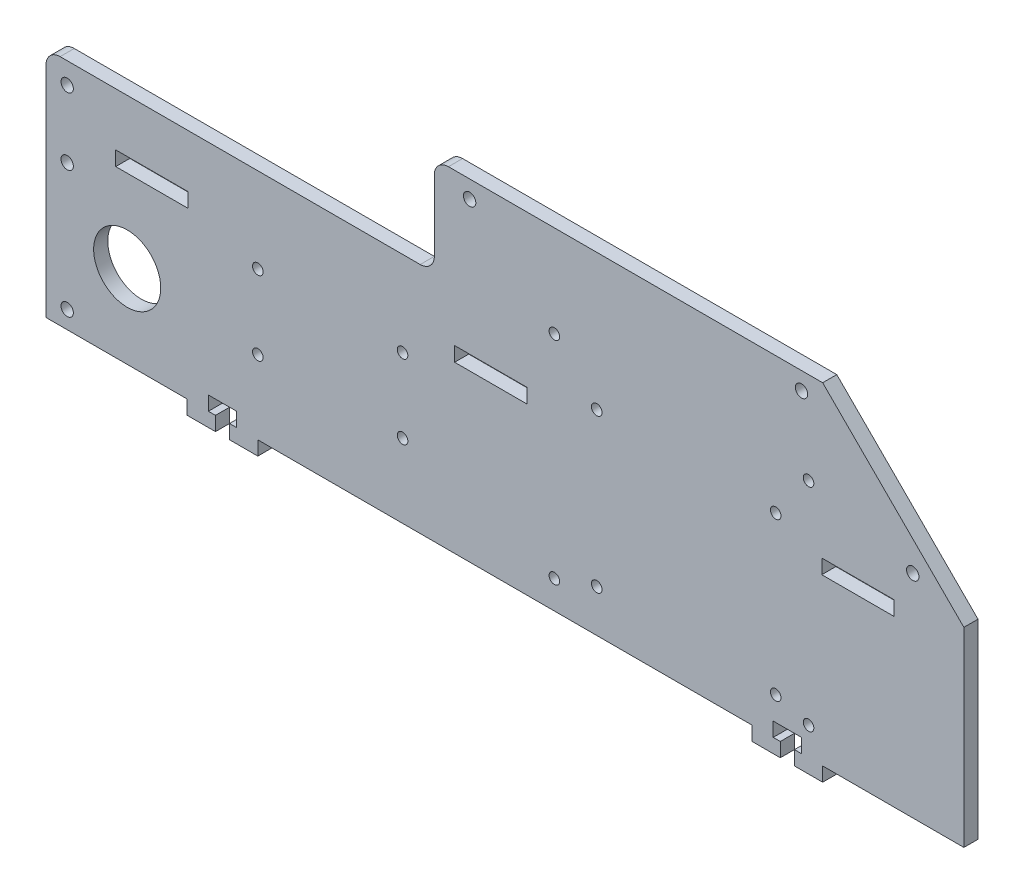
SolidWorks part; units mm, degrees
material "Ст 3 ГОСТ 380-88"
ref_plane "Спереди" through (0, 0, 0) normal (0, 0, 1) x (1, 0, 0)
ref_plane "Сверху" through (0, 0, 0) normal (0, 1, 0) x (1, 0, 0)
ref_plane "Справа" through (0, 0, 0) normal (1, 0, 0) x (0, 0, -1)
other "Configuration Table"
sketch "Эскиз1" plane through (0, 0, 0) normal (0, 0, 1) x (1, 0, 0)
  line L0 (52, -59) -> (60, -59)
  line L2 (0, 0) -> (0, -55)
  line L3 (0, -55) -> (40, -55)
  line L4 (260, -1) -> (260, -55)
  line L6 (40, -55) -> (40, -59)
  line L7 (40, -59) -> (48, -59)
  line L8 (60, -55) -> (60, -59)
  line L10 (200, -55) -> (200, -59)
  line L11 (200, -59) -> (208, -59)
  line L12 (220, -55) -> (220, -59)
  line L14 (48, -59) -> (48, -55)
  line L16 (52, -59) -> (52, -55)
  line L18 (46, -55) -> (46, -51)
  line L19 (46, -51) -> (54, -51)
  line L20 (54, -55) -> (54, -51)
  line L21 (46, -55) -> (48, -55)
  line L23 (52, -55) -> (54, -55)
  line L24 (60, -55) -> (200, -55)
  line L25 (206, -55) -> (208, -55)
  line L26 (212, -55) -> (214, -55)
  line L28 (208, -55) -> (208, -59)
  line L30 (212, -55) -> (212, -59)
  line L32 (206, -55) -> (206, -51)
  line L33 (206, -51) -> (214, -51)
  line L34 (214, -55) -> (214, -51)
  line L35 (220, -55) -> (260, -55)
  line L36 (120, 39) -> (220, 39)
  line L37 (19.75, -4) -> (40.25, -4)
  line L38 (19.75, -4) -> (19.75, -8.1)
  line L39 (212, -59) -> (220, -59)
  line L40 (19.75, -8.1) -> (40.25, -8.1)
  line L41 (40.25, -4) -> (40.25, -8.1)
  line L42 (219.75, -4.119) -> (240.25, -4.119)
  line L43 (219.75, -4.119) -> (219.75, -8.219)
  line L44 (219.75, -8.219) -> (240.25, -8.219)
  line L45 (240.25, -4.119) -> (240.25, -8.219)
  line L46 (115.75, -4) -> (136.25, -4)
  line L47 (115.75, -4) -> (115.75, -8.1)
  line L48 (115.75, -8.1) -> (136.25, -8.1)
  line L49 (136.25, -4) -> (136.25, -8.1)
  line L51 (0, 0) -> (0, 7)
  line L52 (4, 11) -> (106, 11)
  line L54 (114, 39) -> (120, 39)
  line L63 (110, 15) -> (110, 35)
  line L64 (260, -1) -> (220, 39)
  circle A0 centre (23, -31.5) radius 9.5
  arc A2 (106, 11) -> (110, 15) centre (106, 15) ccw
  arc A3 (110, 35) -> (114, 39) centre (114, 35) cw
  arc A4 (0, 7) -> (4, 11) centre (4, 7) cw
  circle A5 centre (23, -31.5) radius 17.5 construction
  circle A6 centre (156, -43) radius 1.5
  circle A8 centre (206.7, 0.4) radius 1.5
  circle A9 centre (156, 0.4) radius 1.5
  circle A12 centre (206.7, -43) radius 1.5
  circle A13 centre (206.7, -44.2) radius 1.5
  circle A14 centre (144, -47) radius 1.5
  circle A18 centre (216, -47) radius 1.5
  circle A19 centre (216, 13) radius 1.5
  circle A20 centre (144, 13) radius 1.5
  point P55 (0, 11)
  point P58 (0, -27.5)
  dimension "D28" = 19
  dimension "D38" = 54
  dimension "D39" = 4
  dimension "D42" = 35
  dimension "D43" = 3
  dimension "D49" = 44.6
  dimension "D51" = 3
  dimension "D53" = 3
  dimension "D2" = 55
  dimension "D3" = 4
  dimension "D4" = 20
  dimension "D5" = 40
  dimension "D6" = 4
  dimension "D7" = 20
  dimension "D8" = 40
  dimension "D9" = 4
  dimension "D10" = 2
  dimension "D11" = 2
  dimension "D12" = 4
  dimension "D13" = 8
  dimension "D14" = 4
  dimension "D15" = 8
  dimension "D16" = 4
  dimension "D17" = 2
  dimension "D18" = 2
  dimension "D19" = 4.1
  dimension "D20" = 28
  dimension "D21" = 19.75
  dimension "D22" = 20.5
  dimension "D23" = 4.1
  dimension "D24" = 20.5
  dimension "D25" = 115.75
  dimension "D26" = 19.75
  dimension "D27" = 20.5
  dimension "D29" = 23.5
  dimension "D30" = 23
  dimension "D31" = 4
  dimension "D32" = 110
  dimension "D33" = 66
  dimension "D34" = 94
  dimension "D35" = 40
  dimension "D36" = 260
  dimension "D37" = 56.5685
  dimension "D40" = 40
  dimension "D41" = 220
  dimension "D44" = 12
  dimension "D47" = 156
  dimension "D48" = 43.4
  dimension "D50" = 50.7
  dimension "D52" = 8
  dimension "D55" = 12
  dimension "D45" = 2
  dimension "D46" = 2
  dimension "D56" = 2
base flange "Базовая кромка1" sketch "Эскиз1" thickness 4 reverse thickness direction no parameters "D1"=0.7366
sketch "Эскиз6" plane through (0, 0, 0) normal (0, 0, 1) x (1, 0, 0)
  line L1 (0, 7) -> (0, -55) construction
  line L2 (0, 7) -> (0, -55) construction
  line L3 (0, -55) -> (40, -55) construction
  line L4 (0, -55) -> (40, -55) construction
  line L5 (220, 39) -> (114, 39) construction
  line L7 (260, -1) -> (220, 39) construction
  circle A0 centre (6, 5) radius 1.75
  circle A1 centre (120, 34) radius 1.75
  circle A2 centre (214, 34) radius 1.75
  circle A3 centre (245.5147, 5) radius 1.75
  circle A4 centre (6, -14) radius 1.75
  circle A5 centre (6, -50) radius 1.75
  dimension "D2" = 3.5
  dimension "D1" = 41
  dimension "D3" = 6
  dimension "D4" = 6
  dimension "D5" = 120
  dimension "D6" = 6
  dimension "D7" = 5
  dimension "D8" = 60
  dimension "D9" = 5
  dimension "D10" = 5
  dimension "D11" = 114
  dimension "D12" = 29
  dimension "D13" = 94
  dimension "D14" = 239.5147
  dimension "D15" = 34
  dimension "D16" = 31.5147
extrude "Вырез-Вытянуть1" cut sketch "Эскиз6" against normal through all normal cut yes
sketch "Эскиз7" plane through (0, 0, 0) normal (0, 0, 1) x (1, 0, 0)
  line L0 (19.75, -8.1) -> (40.25, -8.1) construction
  line L1 (64, -16.1) -> (176, -16.1)
  line L2 (60, -20.1) -> (60, -43)
  line L3 (64, -47) -> (176, -47)
  line L4 (180, -20.1) -> (180, -43)
  line L5 (60, -55) -> (200, -55) construction
  line L6 (0, 7) -> (0, -55) construction
  line L7 (260, -55) -> (260, -1) construction
  arc A0 (176, -47) -> (180, -43) centre (176, -43) ccw
  arc A1 (176, -16.1) -> (180, -20.1) centre (176, -20.1) cw
  arc A2 (64, -16.1) -> (60, -20.1) centre (64, -20.1) ccw
  arc A3 (60, -43) -> (64, -47) centre (64, -43) ccw
  dimension "D5" = 4
  dimension "D1" = 8
  dimension "D2" = 8
  dimension "D3" = 60
  dimension "D4" = 80
extrude "Вырез-Вытянуть2" [suppressed] cut sketch "Эскиз7" against normal through all
sketch "Эскиз8" plane through (0, -55, 0) normal (0, -1, 0) x (1, 0, 0)
  line L0 (46, 0) -> (54, 0) construction
  line L1 (48, -4) -> (48, 0) construction
  line L2 (206, 0) -> (214, 0) construction
  line L3 (208, -4) -> (208, 0) construction
  circle A0 centre (210, -2) radius 1
  circle A1 centre (50, -2) radius 0.8222
  dimension "D5" = 2
  dimension "D1" = 2
  dimension "D2" = 2
  dimension "D3" = 2
  dimension "D4" = 2
extrude "Вырез-Вытянуть3" cut sketch "Эскиз8" against normal blind 10 normal cut yes
sketch "Эскиз9" plane through (0, 0, 0) normal (0, 0, 1) x (1, 0, 0)
  line L0 (19.75, -8.1) -> (40.25, -8.1) construction
  line L1 (0, 7) -> (0, -55) construction
  circle A0 centre (60, -13.1) radius 1.5
  circle A1 centre (101, -34.1) radius 1.5
  circle A2 centre (101, -13.1) radius 1.5
  circle A3 centre (60, -34.1) radius 1.5
  dimension "D5" = 3
  dimension "D6" = 3
  dimension "D7" = 3
  dimension "D8" = 3
  dimension "D1" = 41
  dimension "D2" = 21
  dimension "D3" = 5
  dimension "D4" = 60
extrude "Вырез-Вытянуть4" cut sketch "Эскиз9" against normal up to next normal cut yes
sketch "Сгиб-Линии1" [suppressed] plane through (0, 0, 0) normal (0, 1, 0) x (1, 0, 0)
sketch "Граничная рамка1" [suppressed] plane through (0, 0, 0) normal (0, 1, 0) x (1, 0, 0)
sheet metal parameters "Листовой металл3" thickness 4 parameters "D1"=0.7366
flat pattern "Развертка3" [suppressed]
sketch "Сгиб-Линии2" plane through (0, 0, 0) normal (0, 1, 0) x (1, 0, 0)
sketch "Граничная рамка2" [suppressed] plane through (0, 0, 0) normal (0, 1, 0) x (1, 0, 0)
sheet metal parameters "Листовой металл4" thickness 4 parameters "D1"=0.7366
flat pattern "Развертка3"
sketch "Сгиб-Линии2" plane through (0, 0, 0) normal (0, 1, 0) x (1, 0, 0)
sketch "Граничная рамка2" [suppressed] plane through (0, 0, 0) normal (0, 1, 0) x (1, 0, 0)
sheet metal parameters "Листовой металл5" thickness 4 parameters "D1"=0.7366
flat pattern "Развертка3"
sketch "Сгиб-Линии2" plane through (0, 0, 0) normal (0, 1, 0) x (1, 0, 0)
sketch "Граничная рамка2" [suppressed] plane through (0, 0, 0) normal (0, 1, 0) x (1, 0, 0)
sheet metal parameters "Листовой металл6" thickness 4 parameters "D1"=0.7366
flat pattern "Развертка3"
sketch "Сгиб-Линии2" plane through (0, 0, 0) normal (0, 1, 0) x (1, 0, 0)
sketch3d "Граничная рамка2" [suppressed]
  line L0 (-3.9999, 32.0001, 0) -> (256, 32, 0) construction
  line L1 (-4, -65.9999, 0) -> (256, -66, 0) construction
  line L2 (-3.9999, 32.0001, 0) -> (-4, -65.9999, 0) construction
  line L3 (256, 32, 0) -> (256, -66, 0) construction
sheet metal parameters "Листовой металл7" thickness 4 parameters "D1"=0.7366
flat pattern "Развертка3"
sketch "Сгиб-Линии2" plane through (0, 0, 0) normal (0, 1, 0) x (1, 0, 0)
sketch3d "Граничная рамка2" [suppressed]
  line L0 (-3.9999, 32.0001, 0) -> (256, 32, 0) construction
  line L1 (-4, -65.9999, 0) -> (256, -66, 0) construction
  line L2 (-3.9999, 32.0001, 0) -> (-4, -65.9999, 0) construction
  line L3 (256, 32, 0) -> (256, -66, 0) construction
